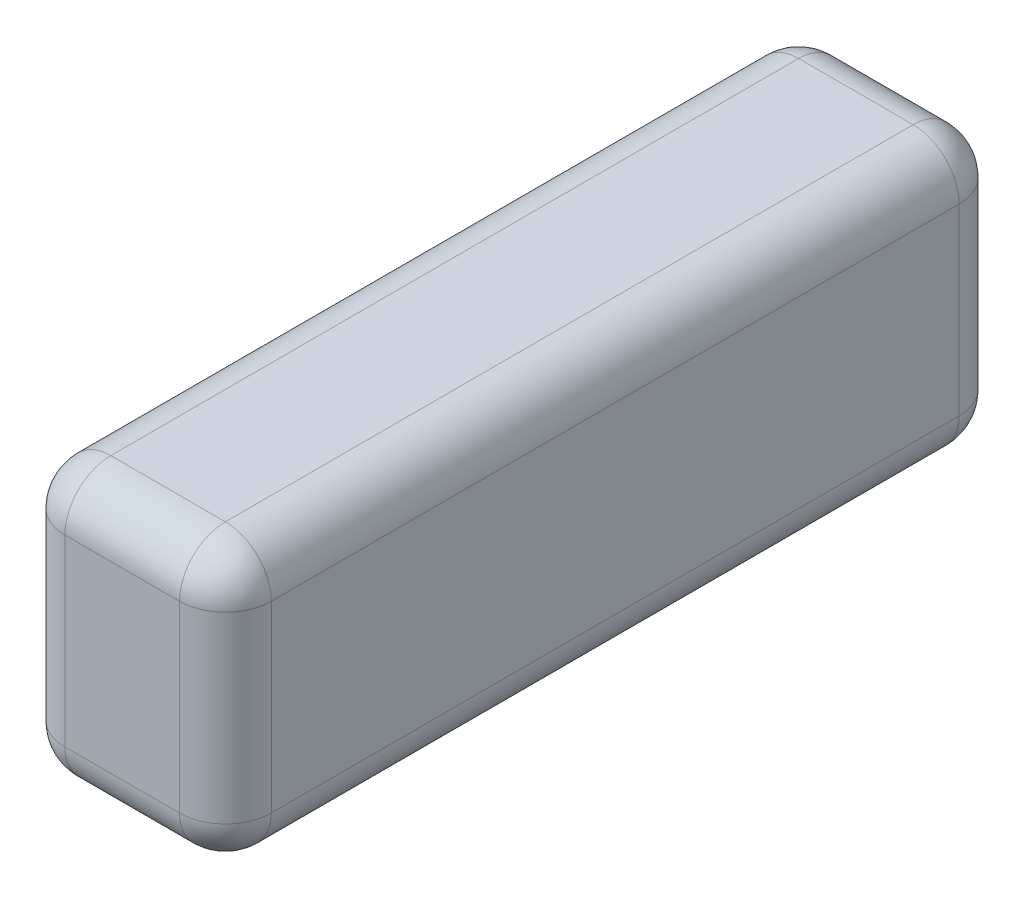
SolidWorks part; units mm, degrees
ref_plane "Face" through (0, 0, 0) normal (0, 0, 1) x (1, 0, 0)
ref_plane "Dessus" through (0, 0, 0) normal (0, 1, 0) x (1, 0, 0)
ref_plane "Droite" through (0, 0, 0) normal (1, 0, 0) x (0, 0, -1)
sketch "Esquisse1" plane through (0, 0, 0) normal (0, 0, 1) x (1, 0, 0)
  line L1 (0, 0) -> (45, 0)
  line L2 (0, 0) -> (0, 60)
  line L3 (0, 60) -> (45, 60)
  line L4 (45, 0) -> (45, 60)
  dimension "D1" = 45
  dimension "D2" = 60
extrude "Boss.-Extru.1" add sketch "Esquisse1" along normal blind 170
fillet "Congé1" radius 10 12 edges at (45, 30, 0) (45, 60, 85) (0, 60, 85) (22.5, 60, 0) (0, 0, 85) (45, 0, 85) (22.5, 0, 0) (22.5, 60, 170) (45, 30, 170) (22.5, 0, 170) (0, 30, 170) (0, 30, 0) tangent propagation no
